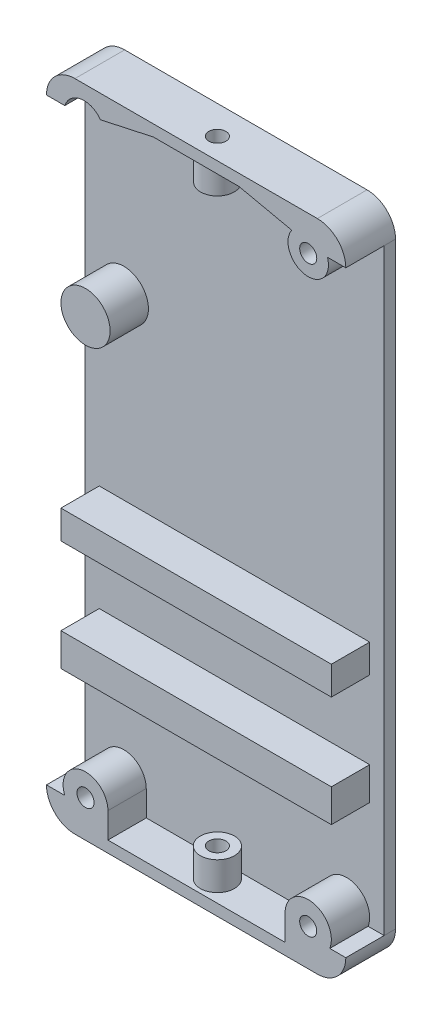
SolidWorks part; units mm, degrees
ref_plane "Front Plane" through (0, 0, 0) normal (0, 0, 1) x (1, 0, 0)
ref_plane "Top Plane" through (0, 0, 0) normal (0, 1, 0) x (1, 0, 0)
ref_plane "Right Plane" through (0, 0, 0) normal (1, 0, 0) x (0, 0, -1)
ref_plane "Plane1" through (0, 0, -28.86) normal (0, 0, 1) x (1, 0, 0)
sketch "Sketch1" plane through (0, 0, -28.86) normal (0, 0, 1) x (1, 0, 0)
  line L6 (-10.6157, 166.9489) -> (-10.6157, 62.0139)
  line L7 (-15.6157, 57.0139) -> (-58.1937, 57.0139)
  line L8 (-63.1937, 166.9489) -> (-63.1937, 62.0139)
  line L9 (-15.6157, 171.9489) -> (-58.1937, 171.9489)
  arc A0 (-63.1937, 62.0139) -> (-58.1937, 57.0139) centre (-58.1937, 62.0139) ccw
  arc A1 (-15.6157, 57.0139) -> (-10.6157, 62.0139) centre (-15.6157, 62.0139) ccw
  arc A2 (-10.6157, 166.9489) -> (-15.6157, 171.9489) centre (-15.6157, 166.9489) ccw
  arc A3 (-63.1937, 166.9489) -> (-58.1937, 171.9489) centre (-58.1937, 166.9489) cw
  dimension "D2" = 5
extrude "Boss-Extrude1" add sketch "Sketch1" against normal blind 2
sketch "Sketch2" plane through (0, 0, -28.86) normal (0, 0, 1) x (1, 0, 0)
  line L0 (-60.6537, 59.5539) -> (-60.6537, 169.4089) construction
  line L1 (-60.6537, 105.3853) -> (-13.1557, 105.3853)
  line L2 (-60.6537, 105.3853) -> (-60.6537, 100.3825)
  line L3 (-60.6537, 100.3825) -> (-13.1557, 100.3825)
  line L4 (-13.1557, 105.3853) -> (-13.1557, 100.3825)
  line L5 (-13.1557, 169.4089) -> (-13.1557, 59.5539) construction
  line L7 (-13.1557, 86.7384) -> (-60.6537, 86.7384)
  line L8 (-13.1557, 86.7384) -> (-13.1557, 80.9775)
  line L9 (-13.1557, 80.9775) -> (-60.6537, 80.9775)
  line L10 (-60.6537, 86.7384) -> (-60.6537, 80.9775)
  circle A0 centre (-17.2197, 165.8529) radius 3.556
  circle A1 centre (-17.2197, 165.8529) radius 1.5
  circle A2 centre (-56.3357, 136.6429) radius 4.318
  circle A3 centre (-17.2197, 63.4909) radius 4.064
  circle A4 centre (-17.2197, 63.4909) radius 1.5
  circle A5 centre (-56.3357, 63.4909) radius 3.937
  circle A6 centre (-56.3357, 63.4909) radius 1.5
  dimension "D1" = 3
  dimension "D2" = 3
  dimension "D3" = 3
extrude "Boss-Extrude2" add sketch "Sketch2" along normal up to surface (6.7324 mm away)
sketch "Sketch3" plane through (0, 0, -28.86) normal (0, 0, 1) x (1, 0, 0)
  line L0 (-29.4047, 169.9489) -> (-44.4047, 169.9489)
  line L4 (-12.6157, 166.9489) -> (-10.6157, 166.9489)
  line L8 (-44.4047, 171.9489) -> (-29.4047, 171.9489)
  line L10 (-15.6157, 171.9489) -> (-58.1937, 171.9489) construction
  line L11 (-12.6157, 166.9489) -> (-13.8368, 166.9489)
  line L12 (-29.4047, 169.9489) -> (-20.1086, 167.9264)
  line L13 (-44.4047, 169.9489) -> (-53.7008, 167.9264)
  line L14 (-61.1937, 166.9489) -> (-59.9726, 166.9489)
  line L16 (-61.1937, 166.9489) -> (-63.1937, 166.9489)
  line L17 (-58.1937, 171.9489) -> (-44.4047, 171.9489)
  line L19 (-29.4047, 171.9489) -> (-15.6157, 171.9489)
  line L20 (-58.1937, 57.0139) -> (-15.6157, 57.0139) construction
  line L21 (-58.1937, 57.0139) -> (-15.6157, 57.0139)
  line L22 (-52.3987, 59.0139) -> (-21.2837, 59.0139)
  line L23 (-63.1937, 62.0139) -> (-61.1937, 62.0139)
  line L24 (-10.6157, 62.0139) -> (-12.6157, 62.0139)
  line L25 (-12.6157, 62.0139) -> (-13.4336, 62.0139)
  line L26 (-21.2837, 63.4909) -> (-21.2837, 59.0139)
  line L27 (-52.3987, 63.4909) -> (-52.3987, 59.0139)
  line L28 (-61.1937, 62.0139) -> (-59.9851, 62.0139)
  line L29 (-58.1937, 59.0139) -> (-15.6157, 59.0139) construction
  arc A2 (-10.6157, 166.9489) -> (-15.6157, 171.9489) centre (-15.6157, 166.9489) ccw construction
  arc A3 (-10.6157, 166.9489) -> (-15.6157, 171.9489) centre (-15.6157, 166.9489) ccw
  circle A6 centre (-17.2197, 165.8529) radius 3.556 construction
  arc A7 (-13.8368, 166.9489) -> (-20.1086, 167.9264) centre (-17.2197, 165.8529) ccw
  arc A8 (-59.9726, 166.9489) -> (-53.7008, 167.9264) centre (-56.5897, 165.8529) cw
  arc A9 (-63.1937, 166.9489) -> (-58.1937, 171.9489) centre (-58.1937, 166.9489) cw
  arc A10 (-15.6157, 57.0139) -> (-10.6157, 62.0139) centre (-15.6157, 62.0139) ccw construction
  arc A11 (-63.1937, 62.0139) -> (-58.1937, 57.0139) centre (-58.1937, 62.0139) ccw construction
  arc A12 (-15.6157, 57.0139) -> (-10.6157, 62.0139) centre (-15.6157, 62.0139) ccw
  arc A13 (-63.1937, 62.0139) -> (-58.1937, 57.0139) centre (-58.1937, 62.0139) ccw
  circle A16 centre (-17.2197, 63.4909) radius 4.064 construction
  circle A17 centre (-56.3357, 63.4909) radius 3.937 construction
  arc A18 (-61.1937, 62.0139) -> (-58.1937, 59.0139) centre (-58.1937, 62.0139) ccw construction
  arc A19 (-59.9851, 62.0139) -> (-52.3987, 63.4909) centre (-56.3357, 63.4909) ccw
  arc A20 (-21.2837, 63.4909) -> (-13.4336, 62.0139) centre (-17.2197, 63.4909) ccw
  arc A21 (-15.6157, 59.0139) -> (-12.6157, 62.0139) centre (-15.6157, 62.0139) ccw construction
  dimension "D1" = 2
extrude "Boss-Extrude3" add sketch "Sketch3" along normal up to surface (6.7324 mm away) contours A19 L27 L22 L26 A20 L25 L24 A12 L21 A13 L23 L28 | A8 L13 L0 L12 A7 L11 L4 A3 L19 L8 L17 A9 L16 L14
sketch "Sketch4" plane through (0, 57.0139, 0) normal (0, -1, 0) x (1, 0, 0)
  line L0 (-58.1937, -30.86) -> (-15.6157, -30.86) construction
  line L2 (-15.6157, -30.86) -> (-15.6157, -22.1276) construction
  circle A0 centre (-36.9047, -25.86) radius 1.5
  point P6 (-36.0612, -27.1004)
  dimension "D1" = 3
  dimension "D2" = 5
  dimension "D3" = 21.289
extrude "Cut-Extrude1" cut sketch "Sketch4" against normal blind 10
sketch "Sketch5" plane through (0, 171.9489, 0) normal (0, 1, 0) x (1, 0, 0)
  line L0 (-15.6157, 30.86) -> (-58.1937, 30.86) construction
  line L1 (-15.6157, 30.86) -> (-15.6157, 22.1276) construction
  circle A0 centre (-36.9047, 25.86) radius 1.5
  dimension "D1" = 3
  dimension "D2" = 5
  dimension "D3" = 21.289
extrude "Cut-Extrude2" cut sketch "Sketch5" against normal blind 10
sketch "Sketch6" plane through (0, 169.9489, 0) normal (0, -1, 0) x (1, 0, 0)
  circle A0 centre (-36.9047, -25.86) radius 2.95
  circle A1 centre (-36.9047, -25.86) radius 1.5
  dimension "D1" = 5.9
extrude "Boss-Extrude5" add sketch "Sketch6" along normal blind 5
sketch "Sketch7" plane through (0, 59.0139, 0) normal (0, 1, 0) x (1, 0, 0)
  circle A0 centre (-36.9047, 25.86) radius 2.995
  circle A1 centre (-36.9047, 25.86) radius 1.5
  dimension "D1" = 5.99
extrude "Boss-Extrude6" add sketch "Sketch7" along normal blind 5
